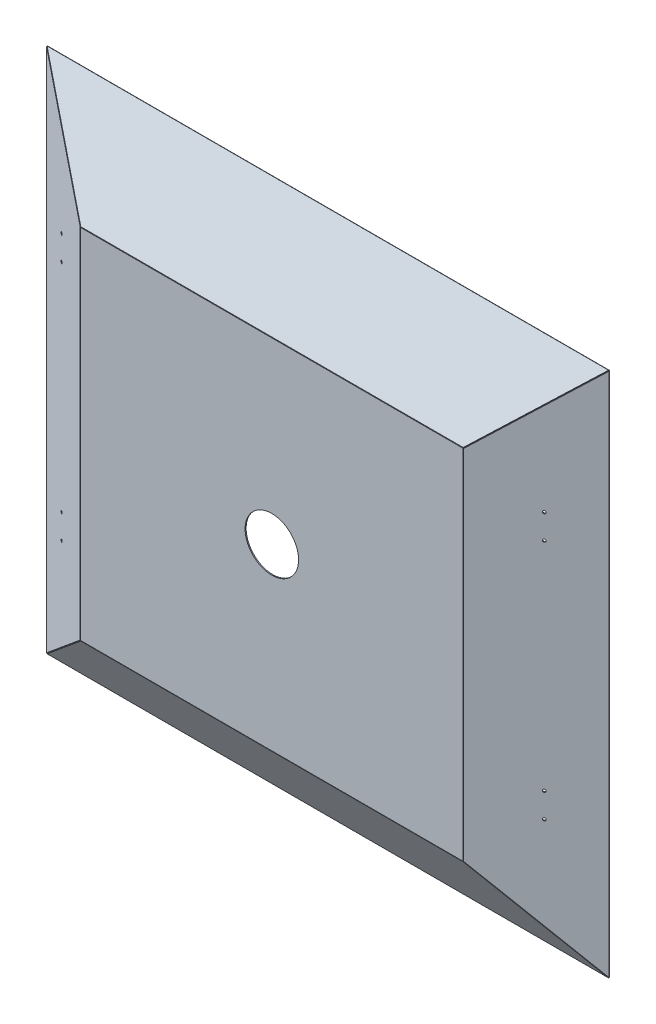
SolidWorks part; units mm, degrees
material "Pine"
ref_plane "Front Plane" through (0, 0, 0) normal (0, 0, 1) x (1, 0, 0)
ref_plane "Top Plane" through (0, 0, 0) normal (0, 1, 0) x (1, 0, 0)
ref_plane "Right Plane" through (0, 0, 0) normal (1, 0, 0) x (0, 0, -1)
sketch "Sketch1" plane through (0, 0, 0) normal (0, 0, 1) x (1, 0, 0)
  line L0 (711, -500) -> (711, 500) construction
  line L1 (-711, 665) -> (711, 665)
  line L2 (-711, 665) -> (-711, -665)
  line L3 (-711, -665) -> (711, -665)
  line L4 (711, 665) -> (711, -665)
  line L5 (-711, 665) -> (711, -665) construction
  line L6 (-711, -665) -> (711, 665) construction
  line L7 (660, -665) -> (-660, -665) construction
  point P0 (0, 0)
ref_axis "Axis1" through (0, 0, 80.9) along (0, 0, -1)
ref_plane "Plane4" through (0, 0, 100) normal (0, 0, 1) x (1, 0, 0)
sketch "Sketch2" plane through (0, 0, 100) normal (0, 0, 1) x (1, 0, 0)
  line L0 (-711, 665) -> (711, 665) construction
  line L1 (-550.6241, -515) -> (550.6241, -515)
  line L2 (-550.6241, -515) -> (-550.6241, 515)
  line L3 (-550.6241, 515) -> (550.6241, 515)
  line L4 (550.6241, -515) -> (550.6241, 515)
  line L5 (-550.6241, -515) -> (550.6241, 515) construction
  line L6 (-550.6241, 515) -> (550.6241, -515) construction
  line L7 (-711, -665) -> (711, 665) construction
  point P0 (0, 0)
  dimension "D1" = 150
ref_axis "Axis2" through (-711, 665, 0) along (0.6647, -0.6217, 0.4144)
ref_axis "Axis3" through (550.6241, 515, 100) along (0.6647, 0.6217, -0.4144)
ref_axis "Axis4" through (550.6241, -515, 100) along (0.6647, -0.6217, -0.4144)
ref_axis "Axis5" through (-550.6241, -515, 100) along (-0.6647, -0.6217, -0.4144)
ref_plane "Plane5" through (0, -204.6154, 306.9231) normal (0, -0.5547, 0.8321) x (1, 0, 0)
ref_plane "Plane6" through (199.0457, 0, 319.2214) normal (0.5291, 0, 0.8486) x (0.8486, 0, -0.5291)
ref_plane "Plane7" through (0, 204.6154, 306.9231) normal (0, -0.5547, -0.8321) x (-1, 0, 0)
ref_plane "Plane8" through (-199.0457, 0, 319.2214) normal (0.5291, 0, -0.8486) x (-0.8486, 0, -0.5291)
sketch "Sketch3" plane through (0, -204.6154, 306.9231) normal (0, -0.5547, 0.8321) x (1, 0, 0)
  line L0 (-711, -553.3134) -> (711, -553.3134) construction
  line L1 (-550.6241, -373.0359) -> (550.6241, -373.0359) construction
  line L2 (-711, -553.3134) -> (711, -553.3134) construction
  line L3 (-550.6241, -373.0359) -> (550.6241, -373.0359)
  line L4 (-550.6241, -373.0359) -> (-711, -553.3134)
  line L5 (550.6241, -373.0359) -> (711, -553.3134)
  line L6 (-711, -553.3134) -> (-808.6097, -663.0359)
  line L7 (-808.6097, -663.0359) -> (808.6097, -663.0359)
  line L8 (808.6097, -663.0359) -> (711, -553.3134)
  dimension "D1" = 290
extrude "Boss-Extrude1" add sketch "Sketch3" along normal blind 3
sketch "Sketch4" plane through (-199.0457, 0, 319.2214) normal (0.5291, 0, -0.8486) x (-0.8486, 0, -0.5291)
  line L0 (603.3237, 665) -> (603.3237, -665) construction
  line L1 (603.3237, 665) -> (603.3237, -665) construction
  line L2 (414.3252, -515) -> (414.3252, 515) construction
  line L3 (414.3252, -515) -> (414.3252, 515)
  line L4 (414.3252, -515) -> (718.354, -756.2946)
  line L5 (718.354, -756.2946) -> (718.354, 756.2946)
  line L6 (718.354, 756.2946) -> (414.3252, 515)
  line L7 (603.3237, 665) -> (414.3252, 515) construction
extrude "Boss-Extrude2" add sketch "Sketch4" against normal blind 3 separate body
sketch "Sketch5" plane through (199.0457, 0, 319.2214) normal (0.5291, 0, 0.8486) x (0.8486, 0, -0.5291)
  line L0 (603.3237, 665) -> (603.3237, -665) construction
  line L1 (414.3252, -515) -> (414.3252, 515) construction
  line L2 (603.3237, 665) -> (603.3237, -665) construction
  line L3 (414.3252, -515) -> (414.3252, 515)
  line L4 (718.354, -756.2946) -> (414.3252, -515)
  line L5 (414.3252, 515) -> (718.354, 756.2946)
  line L6 (718.354, 756.2946) -> (718.354, -756.2946)
  line L7 (414.3252, 515) -> (603.3237, 665) construction
extrude "Boss-Extrude3" add sketch "Sketch5" along normal blind 3 separate body
sketch "Sketch6" plane through (0, 204.6154, 306.9231) normal (0, -0.5547, -0.8321) x (-1, 0, 0)
  line L0 (-550.6241, 373.0359) -> (550.6241, 373.0359)
  line L1 (550.6241, 373.0359) -> (808.6097, 663.0359)
  line L2 (808.6097, 663.0359) -> (-808.6097, 663.0359)
  line L3 (-808.6097, 663.0359) -> (-550.6241, 373.0359)
extrude "Boss-Extrude4" add sketch "Sketch6" against normal blind 3 separate body
ref_plane "Plane9" through (0, 0, 100) normal (0, 0, 1) x (1, 0, 0)
sketch "Sketch7" plane through (0, 0, 100) normal (0, 0, 1) x (1, 0, 0)
  line L1 (-550.6241, -515) -> (550.6241, -515)
  line L2 (-550.6241, -515) -> (-550.6241, 515)
  line L3 (-550.6241, 515) -> (550.6241, 515)
  line L4 (550.6241, -515) -> (550.6241, 515)
extrude "Boss-Extrude5" add sketch "Sketch7" along normal blind 3 separate body
sketch "Sketch9" plane through (199.0457, 0, 319.2214) normal (-0.5291, 0, -0.8486) x (-0.8486, 0, 0.5291)
  circle A0 centre (-582.5259, 383) radius 4
  circle A1 centre (-582.5259, 312) radius 4
  circle A2 centre (-582.5259, -312) radius 4
  circle A3 centre (-582.5259, -383) radius 4
  dimension "D2" = 8
extrude "Cut-Extrude2" cut sketch "Sketch9" against normal through all
sketch "Sketch10" plane through (-199.0457, 0, 319.2214) normal (0.5291, 0, -0.8486) x (-0.8486, 0, -0.5291)
  circle A0 centre (582.5259, -383) radius 4
  circle A1 centre (582.5259, -312) radius 4
  circle A2 centre (582.5259, 312) radius 4
  circle A3 centre (582.5259, 383) radius 4
  dimension "D1" = 8
extrude "Cut-Extrude3" cut sketch "Sketch10" against normal through all
sketch "Sketch11" plane through (0, 0, 103) normal (0, 0, 1) x (1, 0, 0)
  circle A0 centre (0, 0) radius 75 construction
  circle A1 centre (0, 0) radius 75 construction
  circle A2 centre (0, 0) radius 77
  dimension "D1" = 2
extrude "Cut-Extrude4" cut sketch "Sketch11" against normal through all
